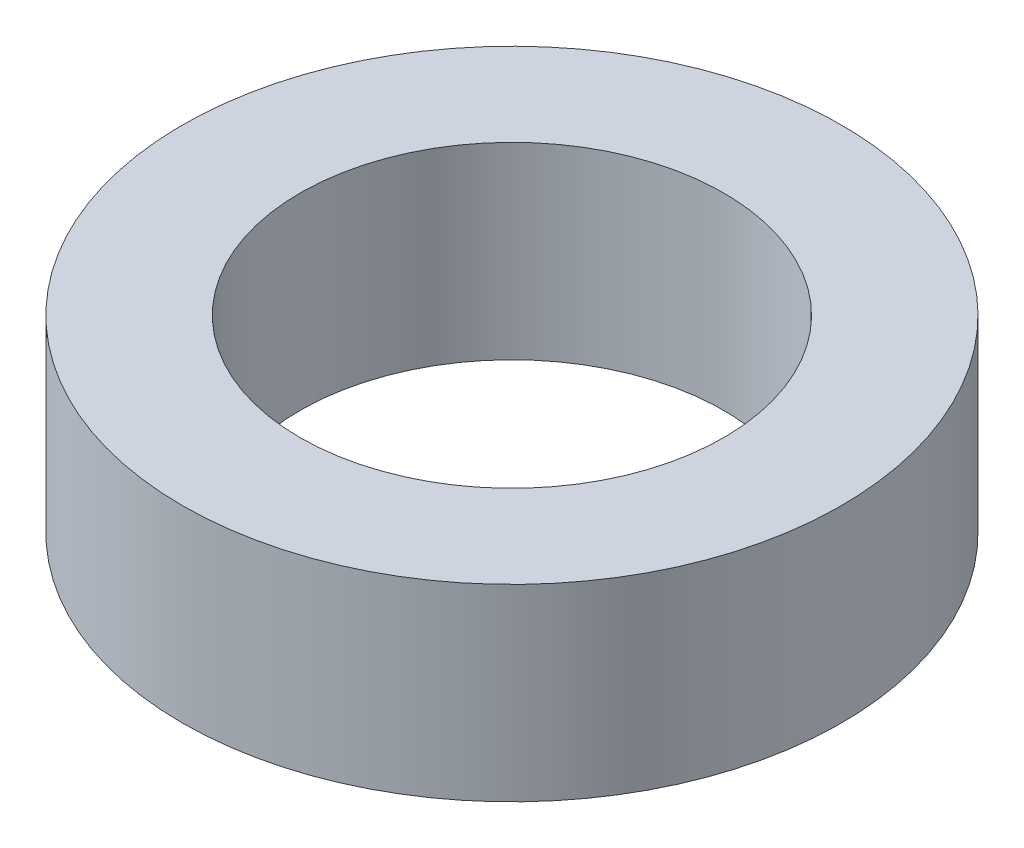
SolidWorks part; units mm, degrees
ref_plane "Front Plane" through (0, 0, 0) normal (0, 0, 1) x (1, 0, 0)
ref_plane "Top Plane" through (0, 0, 0) normal (0, 1, 0) x (1, 0, 0)
ref_plane "Right Plane" through (0, 0, 0) normal (1, 0, 0) x (0, 0, -1)
sketch "Sketch1" plane through (0, 0, 0) normal (0, 1, 0) x (1, 0, 0)
  circle A0 centre (0, 0) radius 4.5
  circle A1 centre (0, 0) radius 7
  dimension "D1" = 9
  dimension "D2" = 14
extrude "Boss-Extrude1" add sketch "Sketch1" along normal blind 4
